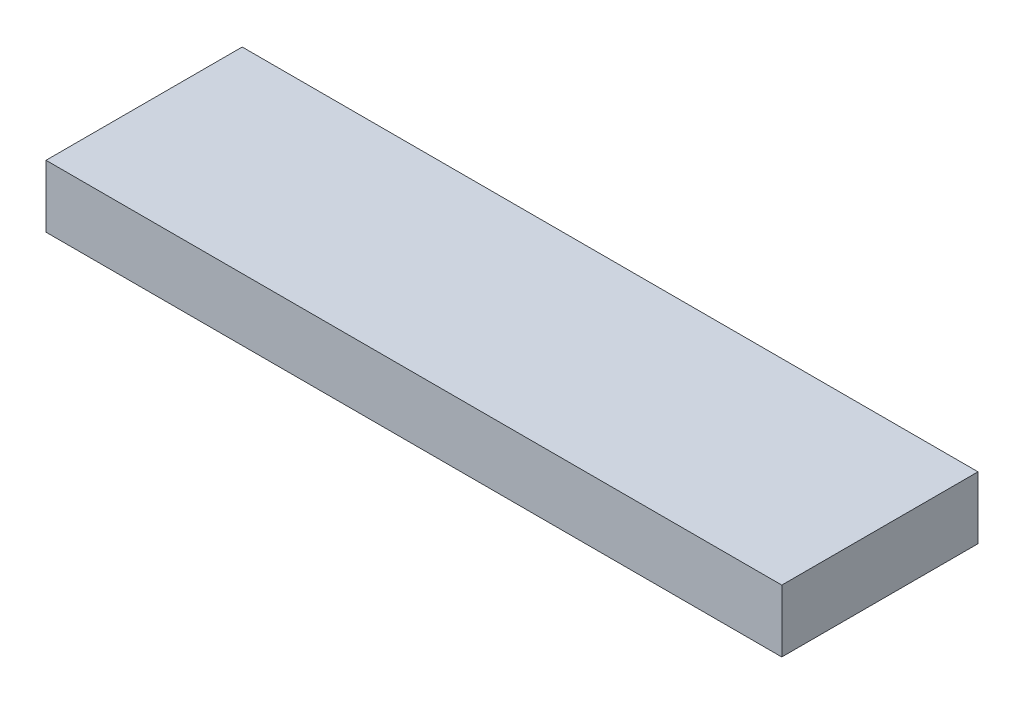
SolidWorks part; units mm, degrees
ref_plane "Front Plane" through (0, 0, 0) normal (0, 0, 1) x (1, 0, 0)
ref_plane "Top Plane" through (0, 0, 0) normal (0, 1, 0) x (1, 0, 0)
ref_plane "Right Plane" through (0, 0, 0) normal (1, 0, 0) x (0, 0, -1)
sketch "Sketch1" plane through (0, 0, 0) normal (1, 0, 0) x (0, 0, -1)
  line L1 (0, 0) -> (40, 0)
  line L2 (0, 0) -> (0, 12.7)
  line L3 (0, 12.7) -> (40, 12.7)
  line L4 (40, 0) -> (40, 12.7)
  dimension "D1" = 12.7
  dimension "D2" = 40
extrude "Boss-Extrude1" add sketch "Sketch1" along normal blind 150
